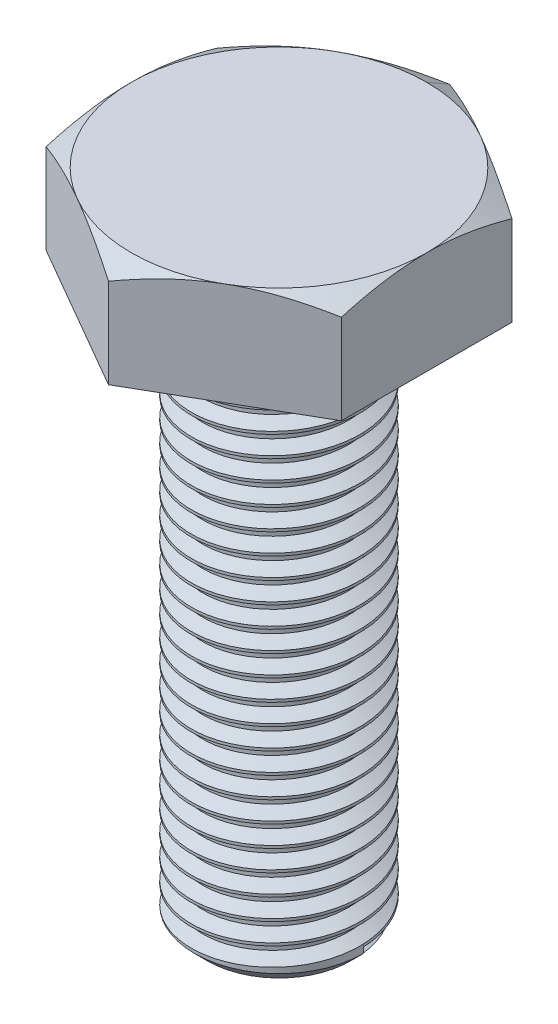
SolidWorks part; units mm, degrees
ref_plane "Front Plane" through (0, 0, 0) normal (0, 0, 1) x (1, 0, 0)
ref_plane "Top Plane" through (0, 0, 0) normal (0, 1, 0) x (1, 0, 0)
ref_plane "Right Plane" through (0, 0, 0) normal (1, 0, 0) x (0, 0, -1)
sketch "Sketch1" plane through (0, 0, 0) normal (0, 1, 0) x (1, 0, 0)
  circle A0 centre (0, 0) radius 12.7
  dimension "D1" = 25.4
extrude "Boss-Extrude1" add sketch "Sketch1" along normal blind 82.55
chamfer "Chamfer1" distance 1.9304 1 edges at (0, 0, 12.7)
thread "Thread2" pitch 3.175 method cut profile "Thread Profile2" start angle 0, offset 0, length 79.375, pitch 3.175, diameter 25.4
ref_plane "Plane2" through (12.7, 0, 0) normal (0, 0, 1) x (1, 0, 0)
sketch "Thread Profile2" plane through (12.7, 0, 0) normal (0, 0, 1) x (1, 0, 0)
  line L0 (0, 0) -> (0, 3.175) construction
  line L11 (0, 0) -> (0, 2.7781)
  line L12 (0, 2.7781) -> (-1.7185, 1.7859)
  line L13 (-1.7185, 1.7859) -> (-1.7185, 0.9922)
  line L15 (-1.7185, 0.9922) -> (0, 0)
  line L17 (-1.7185, 1.3891) -> (0, 1.3891) construction
  point P2 (0, 0)
  dimension "Pitch" = 3.175
  dimension "Profile_Angle" = 60
  dimension "Profile_Land" = 0.7937
  dimension "Profile_Height" = 1.7185
sketch "Sketch7" plane through (0, 82.55, 0) normal (0, 1, 0) x (1, 0, 0)
  line L1 (0, 25.6632) -> (-22.225, 12.8316)
  line L2 (-22.225, 12.8316) -> (-22.225, -12.8316)
  line L3 (-22.225, -12.8316) -> (0, -25.6632)
  line L4 (0, -25.6632) -> (22.225, -12.8316)
  line L5 (22.225, -12.8316) -> (22.225, 12.8316)
  line L6 (22.225, 12.8316) -> (0, 25.6632)
  circle A0 centre (0, 0) radius 22.225 construction
  circle A1 centre (0, 0) radius 22.225 construction
  point P3 (0, 25.6632)
  dimension "D1" = 44.45
extrude "Boss-Extrude2" add sketch "Sketch7" along normal blind 15.4781
sketch "Sketch9" plane through (0, 98.0281, 0) normal (0, 1, 0) x (1, 0, 0)
  line L1 (22.225, 12.8316) -> (0, 25.6632) construction
  line L2 (22.225, -12.8316) -> (22.225, 12.8316) construction
  line L3 (0, -25.6632) -> (22.225, -12.8316) construction
  line L4 (-22.225, -12.8316) -> (0, -25.6632) construction
  line L5 (-22.225, 12.8316) -> (-22.225, -12.8316) construction
  line L6 (0, 25.6632) -> (-22.225, 12.8316) construction
  circle A0 centre (0, 0) radius 22.225
sketch "Sketch10" plane through (0, 0, 0) normal (1, 0, 0) x (0, 0, -1)
  line L0 (22.225, 98.0281) -> (28.5195, 98.0281)
  line L1 (28.5195, 98.0281) -> (28.5195, 94.394)
  line L2 (28.5195, 94.394) -> (22.225, 98.0281)
  point P2 (0, 0)
  point P4 (0, 0)
  dimension "D1" = 30
sweep "Cut-Sweep1" cut profiles "Sketch10" path "Sketch9"
